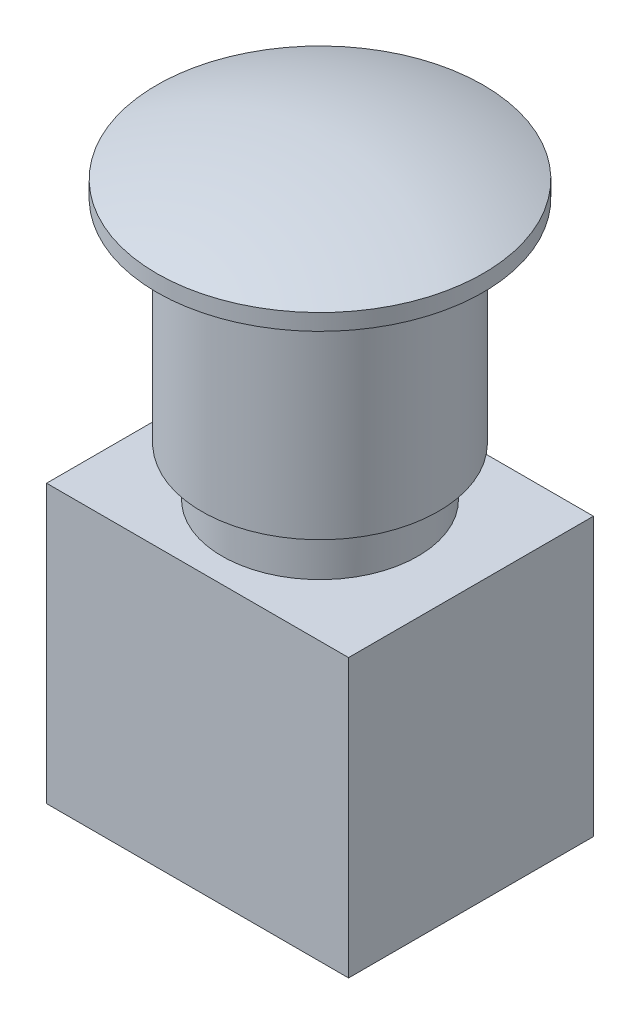
SolidWorks part; units mm, degrees
ref_plane "前视基准面" through (0, 0, 0) normal (0, 0, 1) x (1, 0, 0)
ref_plane "上视基准面" through (0, 0, 0) normal (0, 1, 0) x (1, 0, 0)
ref_plane "右视基准面" through (0, 0, 0) normal (1, 0, 0) x (0, 0, -1)
sketch "草图1" plane through (0, 0, 0) normal (0, 1, 0) x (1, 0, 0)
  line L1 (-18.5, -15) -> (18.5, -15)
  line L2 (-18.5, -15) -> (-18.5, 15)
  line L3 (-18.5, 15) -> (18.5, 15)
  line L4 (18.5, -15) -> (18.5, 15)
  line L5 (-18.5, -15) -> (18.5, 15) construction
  line L6 (-18.5, 15) -> (18.5, -15) construction
  point P0 (0, 0)
  dimension "D1" = 37
  dimension "D2" = 30
extrude "凸台-拉伸1" add sketch "草图1" along normal blind 34
sketch "草图2" plane through (0, 34, 0) normal (0, 1, 0) x (1, 0, 0)
  circle A0 centre (0, 0) radius 12
  dimension "D1" = 24
extrude "凸台-拉伸2" add sketch "草图2" along normal blind 6
sketch "草图3" plane through (0, 40, 0) normal (0, 1, 0) x (1, 0, 0)
  circle A0 centre (0, 0) radius 14.5
  dimension "D1" = 29
extrude "凸台-拉伸3" add sketch "草图3" along normal blind 26
sketch "草图4" plane through (0, 66, 0) normal (0, 1, 0) x (1, 0, 0)
  circle A0 centre (0, 0) radius 20
  dimension "D1" = 40
extrude "凸台-拉伸4" add sketch "草图4" along normal blind 2
dome "圆顶1" faces to dome 1 distance 4 reverse direction no elliptical dome no face at (0, 68, 20) parameters "D1"=4
